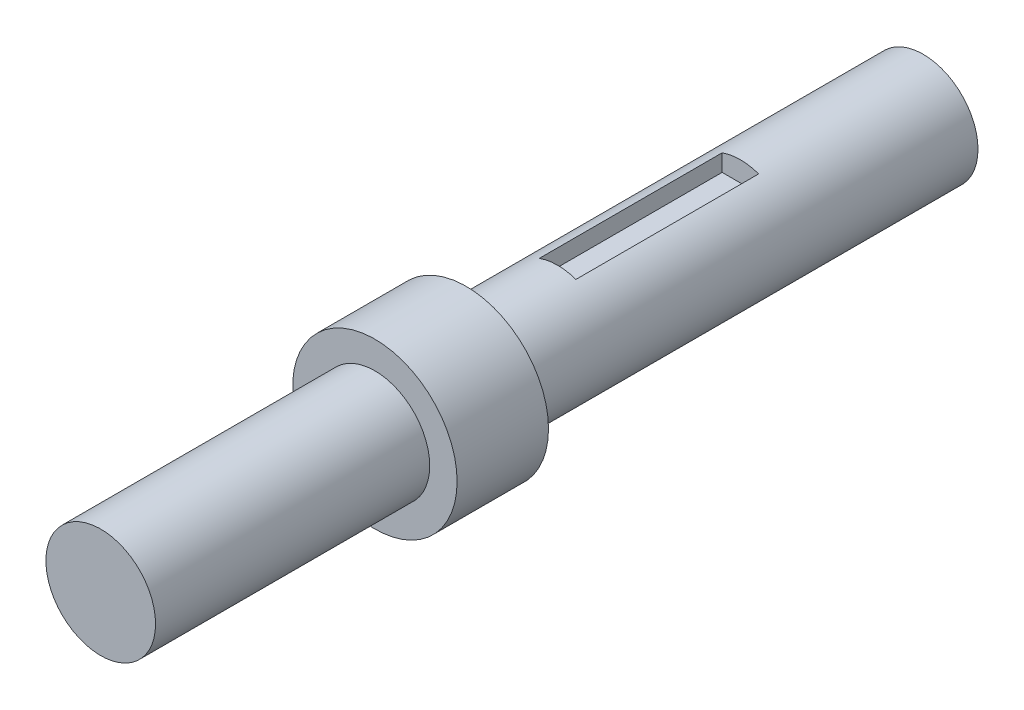
SolidWorks part; units mm, degrees
ref_plane "Front Plane" through (0, 0, 0) normal (0, 0, 1) x (1, 0, 0)
ref_plane "Top Plane" through (0, 0, 0) normal (0, 1, 0) x (1, 0, 0)
ref_plane "Right Plane" through (0, 0, 0) normal (1, 0, 0) x (0, 0, -1)
sketch "Sketch2" plane through (0, 0, 0) normal (0, 0, 1) x (1, 0, 0)
  circle A0 centre (0, 0) radius 6
  dimension "D1" = 12
extrude "Boss-Extrude1" add sketch "Sketch2" along normal blind 50
sketch "Sketch3" plane through (0, 0, 50) normal (0, 0, 1) x (1, 0, 0)
  circle A0 centre (0, 0) radius 9
  dimension "D1" = 18
extrude "Boss-Extrude2" add sketch "Sketch3" along normal blind 10
sketch "Sketch4" plane through (0, 0, 60) normal (0, 0, 1) x (1, 0, 0)
  circle A0 centre (0, 0) radius 6
  dimension "D1" = 12
extrude "Boss-Extrude3" add sketch "Sketch4" along normal blind 30
ref_plane "Plane1" through (0, 6, 0) normal (0, 1, 0) x (1, 0, 0)
sketch "Sketch6" plane through (0, 6, 0) normal (0, 1, 0) x (1, 0, 0)
  line L0 (9, -50) -> (-9, -50) construction
  line L1 (-2, -40) -> (2, -40)
  line L2 (-2, -40) -> (-2, -20)
  line L3 (-2, -20) -> (2, -20)
  line L4 (2, -40) -> (2, -20)
  point P6 (0, -40)
  point P7 (0, -50)
  dimension "D1" = 20
  dimension "D2" = 10
  dimension "D3" = 4
extrude "Cut-Extrude1" cut sketch "Sketch6" against normal blind 2.2
